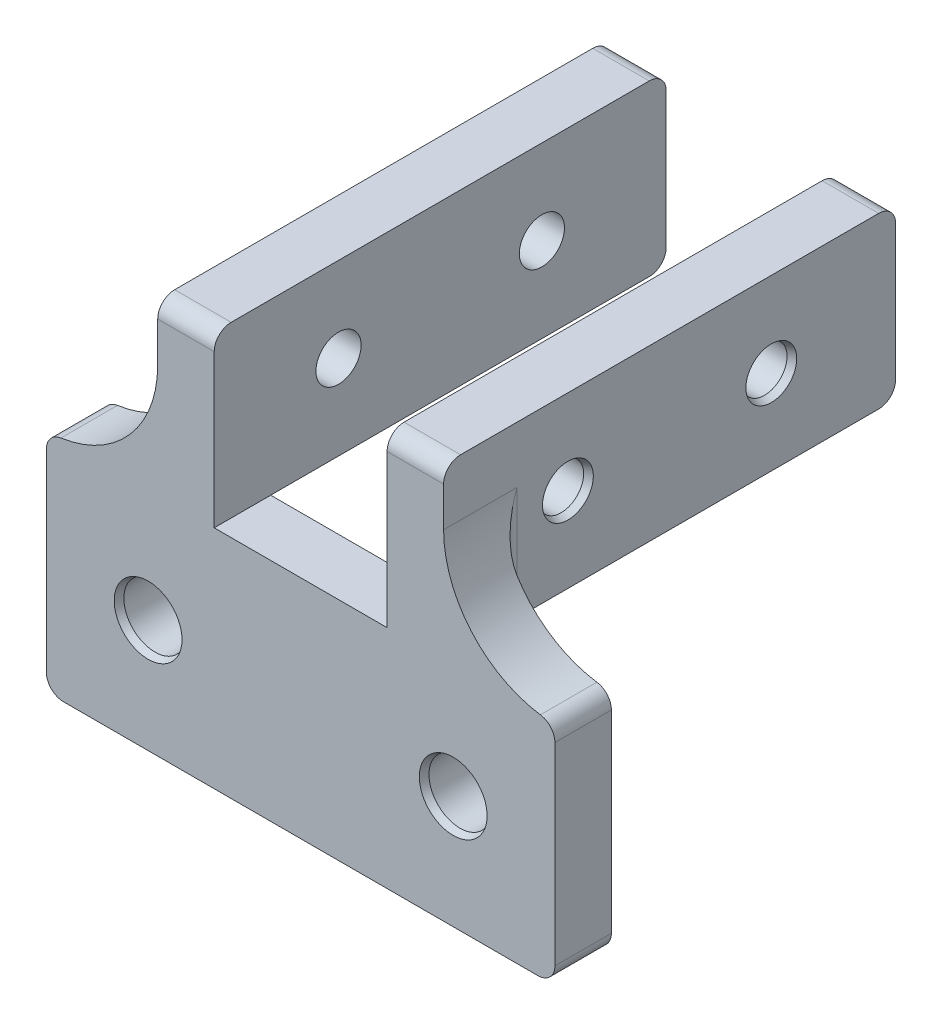
SolidWorks part; units mm, degrees
ref_plane "Front Plane" through (0, 0, 0) normal (0, 0, 1) x (1, 0, 0)
ref_plane "Top Plane" through (0, 0, 0) normal (0, 1, 0) x (1, 0, 0)
ref_plane "Right Plane" through (0, 0, 0) normal (1, 0, 0) x (0, 0, -1)
sketch "Sketch1" plane through (0, 0, 0) normal (0, 0, 1) x (1, 0, 0)
  line L1 (-22.5, -10) -> (22.5, -10)
  line L2 (-22.5, -10) -> (-22.5, 10)
  line L3 (-22.5, 10) -> (22.5, 10)
  line L4 (22.5, -10) -> (22.5, 10)
  line L5 (-22.5, -10) -> (22.5, 10) construction
  line L6 (-22.5, 10) -> (22.5, -10) construction
  point P0 (0, 0)
  dimension "D1" = 20
  dimension "D2" = 45
extrude "Boss-Extrude1" add sketch "Sketch1" along normal blind 5
sketch "Sketch3" plane through (0, 10, 0) normal (0, 1, 0) x (1, 0, 0)
  line L0 (-7.65, 0) -> (7.65, 0) construction
  line L1 (22.5, 0) -> (-22.5, 0) construction
  line L2 (-7.65, 0) -> (-7.65, -5)
  line L3 (22.5, -5) -> (-22.5, -5) construction
  line L4 (-7.65, -5) -> (-12.65, -5)
  line L5 (-12.65, -5) -> (-12.65, 35)
  line L6 (-12.65, 35) -> (-7.65, 35)
  line L7 (-7.65, 35) -> (-7.65, 0)
  line L8 (0, 0) -> (0, -5) construction
  line L9 (7.65, -5) -> (12.65, -5)
  line L10 (7.65, 0) -> (7.65, -5)
  line L11 (12.65, -5) -> (12.65, 35)
  line L12 (7.65, 35) -> (7.65, 0)
  line L13 (12.65, 35) -> (7.65, 35)
  point P6 (0, 0)
  dimension "D1" = 15.3
  dimension "D2" = 5
  dimension "D3" = 40
extrude "Boss-Extrude2" add sketch "Sketch3" along normal blind 15
sketch "Sketch5" plane through (-12.65, 0, 0) normal (-1, 0, 0) x (0, 0, 1)
  line L3 (5, 17.5) -> (-6, 17.5) construction
  line L4 (5, 25) -> (5, 10) construction
  line L5 (-35, 17.5) -> (-24, 17.5) construction
  line L6 (-35, 25) -> (-35, 10) construction
  point P1 (-6, 17.5)
  point P5 (-24, 17.5)
  dimension "D1" = 11
hole_wizard "Ø4.0 (4) Diameter Hole1" positions "Sketch5" profile "Sketch8" hole size "Ø4.0" standard "ANSI Metric" end condition up to next
sketch "Sketch8" plane through (-12.65, 17.5, -24) normal (0, 1, 0) x (0, 0, 1)
  line L0 (0, 0) -> (0, 5)
  line L1 (0, 5) -> (2, 5)
  line L2 (2, 5) -> (2, 0.6036)
  line L3 (2, 0.6036) -> (2.25, 0)
  line L5 (2.25, 0) -> (0, 0)
  line L6 (-2, 0.6036) -> (-2.25, 0) construction
  line L11 (0, -6.35) -> (0, 107.95) construction
  dimension "Thru Hole Dia." = 4
  dimension "Thru Hole Depth" = 5
  dimension "Near C'Sink Dia." = 4.5
  dimension "Near C'Sink Angle" = 45
mirror "Mirror3" about plane through (0, 0, 0) normal (1, 0, 0) of "Ø4.0 (4) Diameter Hole1"
sketch "Sketch11" plane through (0, 0, 5) normal (0, 0, 1) x (1, 0, 0)
  line L0 (-22.5, 0) -> (-13.5, 0) construction
  line L1 (-22.5, 10) -> (-22.5, -10) construction
  line L2 (22.5, 0) -> (13.5, 0) construction
  line L3 (22.5, -10) -> (22.5, 10) construction
  point P1 (-13.5, 0)
  point P6 (13.5, 0)
  dimension "D1" = 9
hole_wizard "Ø5.5 (5.5) Diameter Hole2" positions "Sketch11" profile "Sketch12" hole size "Ø5.5" standard "ANSI Metric" end condition up to next
sketch "Sketch12" plane through (13.5, 0, 5) normal (1, 0, 0) x (0, -1, 0)
  line L0 (0, 0) -> (0, 5)
  line L1 (0, 5) -> (2.75, 5)
  line L2 (2.75, 5) -> (2.75, 0.6036)
  line L3 (2.75, 0.6036) -> (3, 0)
  line L5 (3, 0) -> (0, 0)
  line L6 (-2.75, 0.6036) -> (-3, 0) construction
  line L11 (0, -6.35) -> (0, 107.95) construction
  dimension "Thru Hole Dia." = 5.5
  dimension "Thru Hole Depth" = 5
  dimension "Near C'Sink Dia." = 6
  dimension "Near C'Sink Angle" = 45
fillet "Fillet1" radius 10 2 edges at (12.65, 10, 2.5) (-12.65, 10, 2.5)
fillet "Fillet2" radius 1.5 12 edges at (12.65, 14.9994, 0) (-10.15, 10, -35) (-12.65, 14.9994, 0) (10.15, 10, -35) (10.15, 25, 5) (10.15, 25, -35) (-10.15, 25, 5) (-10.15, 25, -35) (22.5, -10, 2.5) (-22.5, -10, 2.5) (22.5, 10, 2.5) (-22.5, 10, 2.5)
